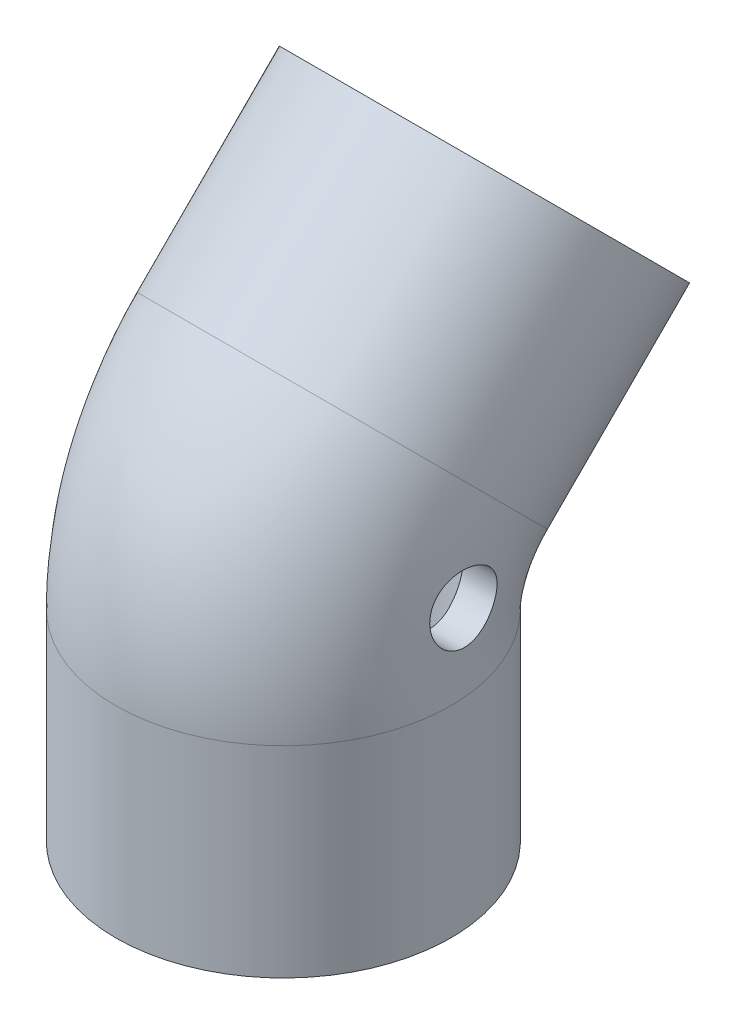
SolidWorks part; units mm, degrees
ref_plane "Plano frontal" through (0, 0, 0) normal (0, 0, 1) x (1, 0, 0)
ref_plane "Plano superior" through (0, 0, 0) normal (0, 1, 0) x (1, 0, 0)
ref_plane "Plano direito" through (0, 0, 0) normal (1, 0, 0) x (0, 0, -1)
sketch "Esboço3" plane through (0, 0, 0) normal (1, 0, 0) x (0, 0, -1)
  line L0 (0, 15) -> (0, 0)
  line L1 (0, 15) -> (15, 15) construction
  line L2 (4.3934, 25.6066) -> (15, 36.2132)
  line L3 (15, 15) -> (4.3934, 25.6066) construction
  arc A0 (0, 15) -> (4.3934, 25.6066) centre (15, 15) cw
  point P5 (0, 30)
  dimension "D3" = 15
  dimension "D2" = 15
  dimension "D1" = 30
sketch "Esboço4" plane through (0, 0, 0) normal (0, 1, 0) x (1, 0, 0)
  circle A0 centre (0, 0) radius 12.5
  circle A1 centre (0, 0) radius 10
  dimension "D1" = 25
  dimension "D2" = 20
sweep "Varredura1" add profiles "Esboço4" path "Esboço3"
sketch "Esboço5" plane through (0, 0, 0) normal (1, 0, 0) x (0, 0, -1)
  line L0 (12.6903, 15.9567) -> (-10.4067, 25.5238) construction
  arc A0 (13.2322, 16.7678) -> (12.5, 15) centre (15, 15) ccw construction
  arc A1 (-4.4454, 34.4454) -> (-12.5, 15) centre (15, 15) ccw construction
  circle A2 centre (1.1418, 20.7403) radius 2.5
  dimension "D1" = 5
extrude "Corte-extrusão1" cut sketch "Esboço5" against normal blind 20 and the other way blind 20
